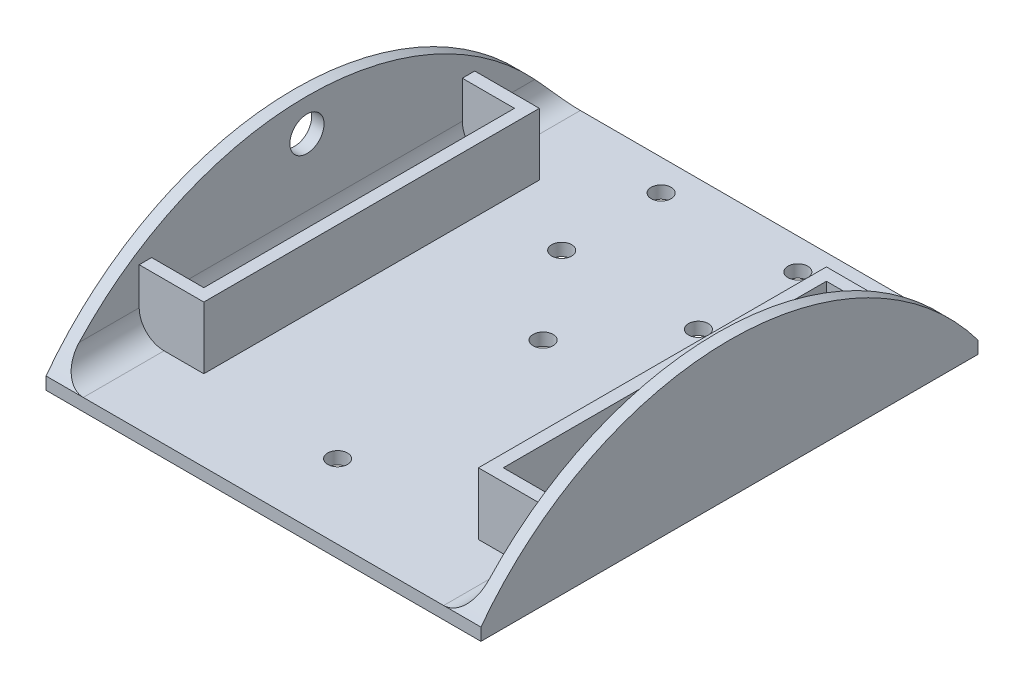
SolidWorks part; units mm, degrees
ref_plane "Front Plane" through (0, 0, 0) normal (0, 0, 1) x (1, 0, 0)
ref_plane "Top Plane" through (0, 0, 0) normal (0, 1, 0) x (1, 0, 0)
ref_plane "Right Plane" through (0, 0, 0) normal (1, 0, 0) x (0, 0, -1)
sketch "Sketch1" plane through (0, 0, 0) normal (0, 1, 0) x (1, 0, 0)
  line L1 (0, 0) -> (88.9, 0)
  line L2 (0, 0) -> (0, 101.6)
  line L3 (0, 101.6) -> (88.9, 101.6)
  line L4 (88.9, 0) -> (88.9, 101.6)
  dimension "D1" = 88.9
  dimension "D2" = 101.6
extrude "Base Extrude" add sketch "Sketch1" along normal blind 2.54
sketch "Sketch2" plane through (88.9, 0, 0) normal (1, 0, 0) x (0, 0, -1)
  line L2 (0, 2.54) -> (101.6, 2.54) construction
  line L3 (101.6, 2.54) -> (101.6, 0)
  line L4 (101.6, 0) -> (0, 0)
  line L5 (0, 0) -> (0, 2.54)
  arc A1 (0, 2.54) -> (101.6, 2.54) centre (50.8, -35.56) cw
  point P6 (50.8, 27.94)
  dimension "D1" = 25.4
extrude "Wall Extrude" add sketch "Sketch2" against normal blind 2.54 contours A1 L3 L4 L5
ref_plane "Wall Plane" through (44.45, 0, 0) normal (1, 0, 0) x (0, 0, -1)
mirror "Wall Mirror" about plane through (44.45, 0, 0) normal (1, 0, 0) of "Wall Extrude"
sketch "Sketch3" plane through (0, 0, 0) normal (-1, 0, 0) x (0, 0, 1)
  line L0 (-50.8, 27.94) -> (-50.8, -0.5285) construction
  circle A0 centre (-50.8, 21.2725) radius 3.4925
  arc A1 (0, 2.54) -> (-101.6, 2.54) centre (-50.8, -35.56) ccw construction
  dimension "D1" = 6.985
  dimension "D2" = 6.6675
extrude "Cut-Extrude1" cut sketch "Sketch3" against normal up to next
fillet "Fillet2" radius 5.08 2 edges at (2.54, 2.54, -50.8) (86.36, 2.54, -50.8)
sketch "Sketch4" plane through (0, 2.54, 0) normal (0, 1, 0) x (1, 0, 0)
  line L0 (44.45, 0) -> (44.45, 101.6) construction
  line L1 (0, 0) -> (88.9, 0) construction
  line L2 (88.9, 101.6) -> (0, 101.6) construction
  line L3 (44.45, 15.15) -> (44.45, 57.15) construction
  line L4 (88.9, 50.8) -> (0, 50.8) construction
  line L5 (88.9, 0) -> (88.9, 101.6) construction
  line L6 (0, 101.6) -> (0, 0) construction
  line L7 (81.28, 101.6) -> (7.62, 101.6) construction
  circle A0 centre (44.45, 57.15) radius 2.032
  circle A1 centre (44.45, 15.15) radius 2.032
  circle A3 centre (58.42, 74.93) radius 2.032
  circle A4 centre (58.42, 95.25) radius 2.032
  circle A5 centre (30.48, 74.93) radius 2.032
  circle A6 centre (30.48, 95.25) radius 2.032
  dimension "D1" = 4.064
  dimension "D2" = 42
  dimension "D4" = 13.97
  dimension "D3" = 44.45
  dimension "D5" = 20.32
  dimension "D6" = 6.35
extrude "Cut-Extrude2" cut sketch "Sketch4" against normal through all
sketch "Sketch5" plane through (0, 2.54, 0) normal (0, 1, 0) x (1, 0, 0)
  line L0 (2.54, 4.241) -> (2.54, 97.359) construction
  line L1 (13.208, 19.05) -> (2.54, 19.05)
  line L2 (13.208, 19.05) -> (13.208, 82.55)
  line L3 (13.208, 82.55) -> (2.54, 82.55)
  line L4 (2.54, 19.05) -> (2.54, 82.55)
  line L5 (44.45, 101.6) -> (44.45, 0) construction
  line L6 (15.748, 85.09) -> (2.54, 85.09)
  line L7 (15.748, 85.09) -> (15.748, 16.51)
  line L8 (15.748, 16.51) -> (2.54, 16.51)
  line L9 (2.54, 85.09) -> (2.54, 16.51)
  line L10 (81.28, 101.6) -> (7.62, 101.6) construction
  line L11 (7.62, 0) -> (81.28, 0) construction
  line L12 (88.9, 0) -> (88.9, 101.6) construction
  line L13 (88.9, 86.36) -> (73.152, 86.36)
  line L14 (88.9, 86.36) -> (88.9, 15.24)
  line L19 (88.9, 15.24) -> (73.152, 15.24)
  line L24 (73.152, 86.36) -> (73.152, 15.24)
  line L25 (88.9, 50.8) -> (0, 50.8) construction
  line L26 (0, 101.6) -> (0, 0) construction
  line L27 (86.36, 97.359) -> (86.36, 4.241) construction
  line L28 (88.9, 52.07) -> (73.152, 52.07)
  line L29 (88.9, 52.07) -> (88.9, 49.53)
  line L30 (88.9, 49.53) -> (73.152, 49.53)
  line L31 (73.152, 52.07) -> (73.152, 49.53)
  line L32 (75.692, 17.78) -> (86.36, 17.78)
  line L33 (75.692, 17.78) -> (75.692, 83.82)
  line L34 (75.692, 83.82) -> (86.36, 83.82)
  line L35 (86.36, 17.78) -> (86.36, 83.82)
  line L36 (86.36, 86.36) -> (86.36, 15.24)
  point P6 (13.208, 50.8)
  point P9 (2.54, 50.8)
  point P28 (44.45, 50.8)
  point P29 (44.45, 50.8)
  dimension "D1" = 63.5
  dimension "D2" = 2.54
  dimension "D3" = 2.54
  dimension "D4" = 68.58
  dimension "D5" = 10.668
  dimension "D6" = 15.748
  dimension "D7" = 71.12
  dimension "D8" = 2.54
  dimension "D9" = 1.27
  dimension "D10" = 2.54
  dimension "D11" = 2.54
  dimension "D12" = 2.54
extrude "Boss-Extrude1" add sketch "Sketch5" along normal blind 12.7
